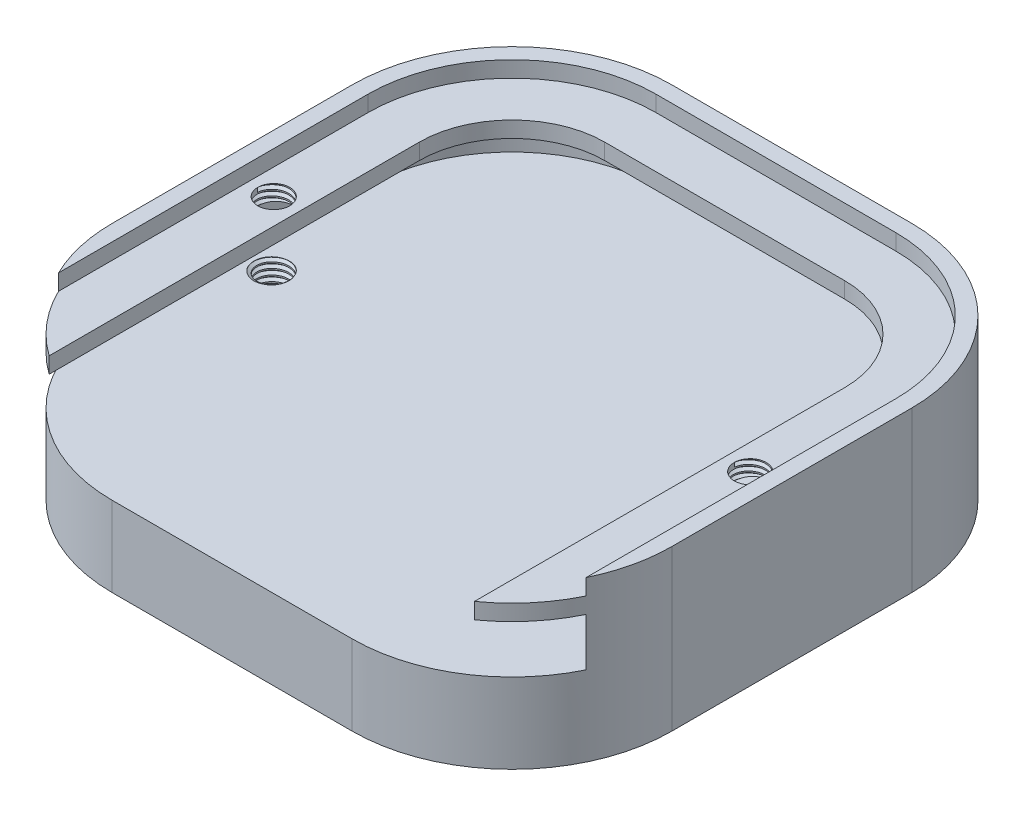
SolidWorks part; units mm, degrees
ref_plane "Front Plane" through (0, 0, 0) normal (0, 0, 1) x (1, 0, 0)
ref_plane "Top Plane" through (0, 0, 0) normal (0, 1, 0) x (1, 0, 0)
ref_plane "Right Plane" through (0, 0, 0) normal (1, 0, 0) x (0, 0, -1)
sketch "Sketch2" plane through (0, 0, 0) normal (0, 1, 0) x (1, 0, 0)
  line L0 (-9.525, 22.225) -> (9.525, 22.225)
  line L5 (22.225, 9.525) -> (22.225, -9.525)
  line L6 (9.525, -22.225) -> (-9.525, -22.225)
  line L7 (-22.225, -9.525) -> (-22.225, 9.525)
  line L8 (0, 22.225) -> (0, -22.225) construction
  line L9 (-22.225, 0) -> (22.225, 0) construction
  arc A3 (9.525, 22.225) -> (22.225, 9.525) centre (9.525, 9.525) cw
  arc A4 (22.225, -9.525) -> (9.525, -22.225) centre (9.525, -9.525) cw
  arc A5 (-9.525, -22.225) -> (-22.225, -9.525) centre (-9.525, -9.525) cw
  arc A6 (-9.525, 22.225) -> (-22.225, 9.525) centre (-9.525, 9.525) ccw
  dimension "D3" = 19.05
  dimension "D4" = 22.225
  dimension "D1" = 12.7
  dimension "D2" = 19.05
  dimension "D5" = 22.225
extrude "Boss-Extrude1" add sketch "Sketch2" along normal blind 6.35
sketch "Sketch3" plane through (0, 6.35, 0) normal (0, 1, 0) x (1, 0, 0)
  line L13 (-9.525, 22.225) -> (9.525, 22.225)
  line L14 (-9.525, 20.955) -> (9.525, 20.955)
  line L15 (-22.225, 9.525) -> (-22.225, -9.525)
  line L16 (-20.955, 9.525) -> (-20.955, -15.0608)
  line L17 (20.955, 9.525) -> (20.955, -15.0608)
  line L18 (22.225, 9.525) -> (22.225, -9.525)
  arc A12 (-9.525, 22.225) -> (-22.225, 9.525) centre (-9.525, 9.525) ccw
  arc A13 (9.525, 22.225) -> (22.225, 9.525) centre (9.525, 9.525) cw
  arc A14 (-9.525, 20.955) -> (-20.955, 9.525) centre (-9.525, 9.525) ccw
  arc A15 (9.525, 20.955) -> (20.955, 9.525) centre (9.525, 9.525) cw
  arc A16 (-22.225, -9.525) -> (-20.955, -15.0608) centre (-9.525, -9.525) ccw
  arc A17 (20.955, -15.0608) -> (22.225, -9.525) centre (9.525, -9.525) ccw
  arc A18 (-22.225, -9.525) -> (-9.525, -22.225) centre (-9.525, -9.525) ccw construction
  arc A19 (9.525, -22.225) -> (22.225, -9.525) centre (9.525, -9.525) ccw construction
  dimension "D1" = 1.27
  dimension "D2" = 1.27
  dimension "D3" = 1.27
extrude "Boss-Extrude2" add sketch "Sketch3" along normal blind 6.35
sketch "Sketch4" plane through (0, 12.7, 0) normal (0, 1, 0) x (1, 0, 0)
  line L13 (-20.955, -15.0608) -> (-20.955, 9.525)
  line L15 (-16.891, -19.8706) -> (-16.891, 9.525)
  line L16 (-9.525, 20.955) -> (9.525, 20.955)
  line L17 (20.955, 9.525) -> (20.955, -15.0608)
  line L18 (16.891, -19.8706) -> (16.891, 9.525)
  line L19 (-9.525, 16.891) -> (9.525, 16.891)
  arc A10 (-22.225, -9.525) -> (-9.525, -22.225) centre (-9.525, -9.525) ccw construction
  arc A11 (9.525, -22.225) -> (22.225, -9.525) centre (9.525, -9.525) ccw construction
  arc A12 (-9.525, 20.955) -> (-20.955, 9.525) centre (-9.525, 9.525) ccw
  arc A13 (9.525, 20.955) -> (20.955, 9.525) centre (9.525, 9.525) cw
  arc A14 (-9.525, 16.891) -> (-16.891, 9.525) centre (-9.525, 9.525) ccw
  arc A15 (9.525, 16.891) -> (16.891, 9.525) centre (9.525, 9.525) cw
  arc A16 (20.955, -15.0608) -> (16.891, -19.8706) centre (9.525, -9.525) cw
  arc A17 (-20.955, -15.0608) -> (-16.891, -19.8706) centre (-9.525, -9.525) ccw
  dimension "D4" = 7.366
  dimension "D1" = 4.064
  dimension "D2" = 4.064
  dimension "D3" = 4.064
extrude "Boss-Extrude3" add sketch "Sketch4" along normal blind 1.27 from offset 2.54 offset against normal yes
sketch "Sketch5" plane through (0, 11.43, 0) normal (0, 1, 0) x (1, 0, 0)
  line L0 (-22.225, 0) -> (22.225, 0) construction
  line L1 (-20.955, -15.0608) -> (-20.955, 9.525) construction
  line L2 (20.955, 9.525) -> (20.955, -15.0608) construction
  circle A0 centre (-18.923, 0) radius 1.27
  circle A1 centre (18.923, 0) radius 1.27
  dimension "D1" = 2.54
  dimension "D2" = 2.032
  dimension "D3" = 2.032
extrude "Cut-Extrude2" cut sketch "Sketch5" against normal blind 10.16
thread "Thread4" pitch 0.4536 method cut profile "Thread Profile4" start angle 0, offset 0, length 10.16, pitch 0.4536, diameter 2.54
ref_plane "Plane4" through (-20.193, 11.43, 0) normal (0, 0, 1) x (-1, 0, 0)
sketch "Thread Profile4" plane through (-20.193, 11.43, 0) normal (0, 0, 1) x (-1, 0, 0)
  line L0 (0, 0) -> (0, 0.4536) construction
  line L1 (0, 0) -> (0.2455, 0.1417)
  line L2 (0.2455, 0.1417) -> (0.2455, 0.1984)
  line L3 (0.2455, 0.1984) -> (0, 0.3402)
  line L4 (0.2455, 0.1701) -> (0, 0.1701) construction
  line L11 (0, 0) -> (0, 0.3402)
  point P2 (0, 0)
  dimension "Pitch" = 0.4536
  dimension "Profile_Angle" = 60
  dimension "Profile_Land" = 0.0567
  dimension "Profile_Height" = 0.2455
thread "Thread5" pitch 0.4536 method cut profile "Thread Profile5" start angle 0, offset 0, length 10.16, pitch 0.4536, diameter 2.54
ref_plane "Plane5" through (17.653, 11.43, 0) normal (0, 0, 1) x (-1, 0, 0)
sketch "Thread Profile5" plane through (17.653, 11.43, 0) normal (0, 0, 1) x (-1, 0, 0)
  line L0 (0, 0) -> (0, 0.4536) construction
  line L1 (0, 0) -> (0.2455, 0.1417)
  line L2 (0.2455, 0.1417) -> (0.2455, 0.1984)
  line L3 (0.2455, 0.1984) -> (0, 0.3402)
  line L4 (0.2455, 0.1701) -> (0, 0.1701) construction
  line L11 (0, 0) -> (0, 0.3402)
  point P2 (0, 0)
  dimension "Pitch" = 0.4536
  dimension "Profile_Angle" = 60
  dimension "Profile_Land" = 0.0567
  dimension "Profile_Height" = 0.2455
